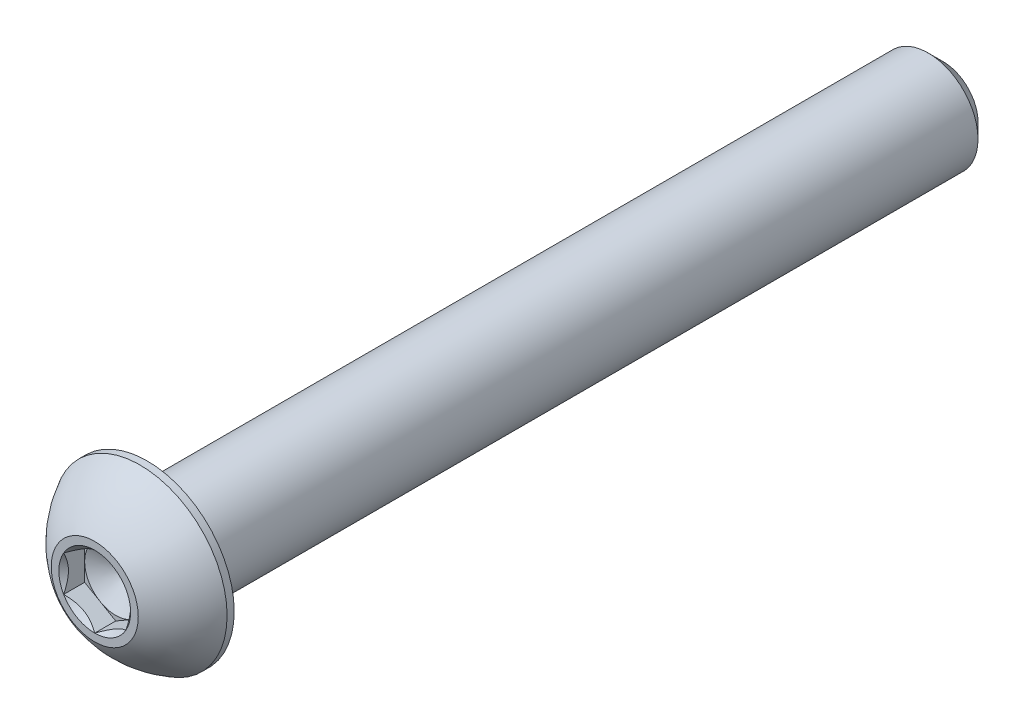
SolidWorks part; units mm, degrees
ref_plane "Front Plane" through (0, 0, 0) normal (0, 0, 1) x (1, 0, 0)
ref_plane "Top Plane" through (0, 0, 0) normal (0, 1, 0) x (1, 0, 0)
ref_plane "Right Plane" through (0, 0, 0) normal (1, 0, 0) x (0, 0, -1)
sketch "Sketch1" plane through (0, 0, 0) normal (1, 0, 0) x (0, 0, -1)
  line L0 (-27.0764, 0) -> (27.0764, 0) construction
  line L1 (-23.7236, 5.5499) -> (-23.7236, -5.5499) construction
  line L2 (-27.0764, 1.9844) -> (-27.0764, -1.9844) construction
  line L3 (27.0764, 3.175) -> (27.0764, -3.175) construction
  line L4 (26.997, 3.3125) -> (27.632, 2.2126) construction
  line L5 (27.632, 2.2126) -> (28.267, 3.3125) construction
  line L6 (28.267, 3.3125) -> (26.997, 3.3125) construction
  line L7 (27.632, 3.3125) -> (27.632, 3.175) construction
  line L8 (27.632, 2.2126) -> (27.632, 2.3501) construction
  line L9 (27.5526, 2.3501) -> (27.7114, 2.3501)
  line L10 (-27.0764, 2.7781) -> (-27.0764, -2.7781) construction
  line L11 (-23.7236, 5.5499) -> (-24.1772, 5.5499) construction
  line L12 (-27.0764, 1.9844) -> (-25.7353, 1.9844) construction
  line L13 (-25.7353, 1.9844) -> (-24.5896, 0) construction
  point P5 (-23.7236, 0)
  point P10 (22.6314, -3.175)
  dimension "Drive Size" = 3.9688
  dimension "Head Diameter" = 11.0998
  dimension "Head Height" = 3.3528
  dimension "Screw Size Decimal Equivalent" = 6.35
  dimension "Length" = 50.8
  dimension "Thread Note" = 4.445
  dimension "Pitch" = 1.27
  dimension "Pitch/8" = 0.1588
  dimension "Approx Head Face Flat" = 5.5563
  dimension "Approx Head Edge Flat" = 0.4536
  dimension "Drive Drill Clearance" = 60
  dimension "Approx Drive Depth" = 1.3411
sketch "Sketch2" plane through (0, 0, 0) normal (1, 0, 0) x (0, 0, -1)
  line L0 (-27.0764, 1.9844) -> (-27.0764, 2.7781)
  line L1 (-24.1772, 5.5499) -> (-23.7236, 5.5499)
  line L2 (-23.7236, 5.5499) -> (-23.7236, 3.175)
  line L3 (-23.7236, 5.5499) -> (-23.7236, -5.5499) construction
  line L4 (-23.7236, 3.175) -> (26.1239, 3.175)
  line L5 (27.0764, 2.2225) -> (27.0764, 0)
  line L6 (-27.0764, 1.9844) -> (-25.7353, 1.9844)
  line L7 (-25.7353, 1.9844) -> (-24.5896, 0)
  line L8 (27.0764, 0) -> (-24.5896, 0)
  line L9 (26.1239, 3.175) -> (27.0764, 2.2225)
  line L10 (26.1239, -3.175) -> (26.1239, 3.175) construction
  line L11 (-27.0764, 2.7781) -> (-25.4761, 5.5499) construction
  arc A0 (-24.1772, 5.5499) -> (-27.0764, 2.7781) centre (-20.8836, -0.7973) ccw
  point P13 (27.0764, 3.175)
  point P25 (26.1239, 0)
  dimension "D1" = 0.9525
  dimension "D2" = 45
  dimension "D3" = 30
revolve "Revolve1" add sketch "Sketch2" angle 360 about L0
sketch "Sketch5" plane through (0, 0, 0) normal (1, 0, 0) x (0, 0, -1)
  line L0 (27.0764, -3.175) -> (-23.7236, -3.175) construction
  line L1 (-23.7236, -3.175) -> (26.1239, -3.175) construction
  line L2 (27.0764, -2.2225) -> (27.0764, 2.2225) construction
  line L3 (-23.7236, -3.175) -> (-23.7236, 3.175) construction
  point P9 (25.1714, -3.175)
  dimension "D1" = 1.905
sketch "Sketch3" plane through (0, 0, 0) normal (0, 0, 1) x (1, 0, 0)
  line L1 (0, 2.2914) -> (-1.9844, 1.1457)
  line L2 (-1.9844, 1.1457) -> (-1.9844, -1.1457)
  line L3 (-1.9844, -1.1457) -> (0, -2.2914)
  line L4 (0, -2.2914) -> (1.9844, -1.1457)
  line L5 (1.9844, -1.1457) -> (1.9844, 1.1457)
  line L6 (1.9844, 1.1457) -> (0, 2.2914)
  circle A0 centre (0, 0) radius 1.9844 construction
  circle A1 centre (0, 0) radius 5.5499 construction
extrude "Cut-Extrude1" cut sketch "Sketch3" along normal through all from vertex starting at point (0, 1.9844, 25.7353)
sketch "Sketch4" plane through (0, 0, 27.0764) normal (0, 0, 1) x (1, 0, 0)
  circle A0 centre (0, 0) radius 2.2914
extrude "Cut-Extrude2" cut sketch "Sketch4" against normal up to next (54.1528 mm away) draft 45
sketch "Sketch6" [suppressed] plane through (0, 0, -27.0764) normal (0, 0, -1) x (-1, 0, 0)
  circle A0 centre (0, 0) radius 3.175
curve "Helix/Spiral1" [suppressed] pitch 1.27 height 52.07 turns 41
sketch "Sketch7" [suppressed] plane through (0, 0, 0) normal (1, 0, 0) x (0, 0, -1)
  line L0 (27.0764, 3.175) -> (28.1876, 3.175)
  line L1 (28.1876, 3.175) -> (27.7114, 2.3501)
  line L2 (27.5526, 2.3501) -> (27.7114, 2.3501)
  line L3 (27.5526, 2.3501) -> (27.0764, 3.175)
  line L4 (27.632, 2.2126) -> (28.267, 3.3125) construction
sweep "Cut-Sweep1" [suppressed] cut profiles "Sketch7" path "Helix/Spiral1"
sketch "Sketch8" [suppressed] plane through (0, 0, 0) normal (1, 0, 0) x (0, 0, -1)
  line L0 (-25.7353, 3.175) -> (-23.7236, 3.175)
  line L1 (-25.7353, 3.175) -> (-25.7353, 1.9844)
  line L2 (-25.7353, 1.9844) -> (-24.5896, 0)
  line L3 (-24.5896, 0) -> (-21.0248, 0)
  line L4 (-23.7236, 3.175) -> (-23.0886, 3.175)
  line L5 (-23.7236, 5.5499) -> (-23.7236, -5.5499) construction
  line L6 (-23.0886, 3.175) -> (-21.0248, 2.2126)
  line L7 (-21.0248, 2.2126) -> (-21.0248, 0)
  dimension "D1" = 0.635
  dimension "D2" = 25
revolve "Revolve2" [suppressed] add sketch "Sketch8" angle 360 about L0
equation "\"Pitch/8@Sketch1\" = \"Pitch@Sketch1\" * .125"
equation "\"Thread Note@Sketch1\" = \"Pitch@Sketch1\" * 3.5"
equation "\"Approx Head Face Flat@Sketch1\" = \"Drive Size@Sketch1\" * 1.4"
equation "\"Approx Head Edge Flat@Sketch1\" =  ( \"Approx Head Face Flat@Sketch1\" - \"Drive Size@Sketch1\" )  / 3.5"
equation "\"Approx Drive Depth@Sketch1\" = \"Head Height@Sketch1\" * .40"
equation "\"D1@Sketch2\"=\"Pitch@Sketch1\"*.750"
equation "\"D4@Helix/Spiral1\"=\"Pitch@Sketch1\""
equation "\"D3@Helix/Spiral1\" = \"D4@Helix/Spiral1\" + \"Length@Sketch1\""
equation "\"D1@Sketch5\" = \"Pitch@Sketch1\" * 1.5"
equation "\"D1@Sketch8\"=\"Pitch@Sketch1\"*0.5"
